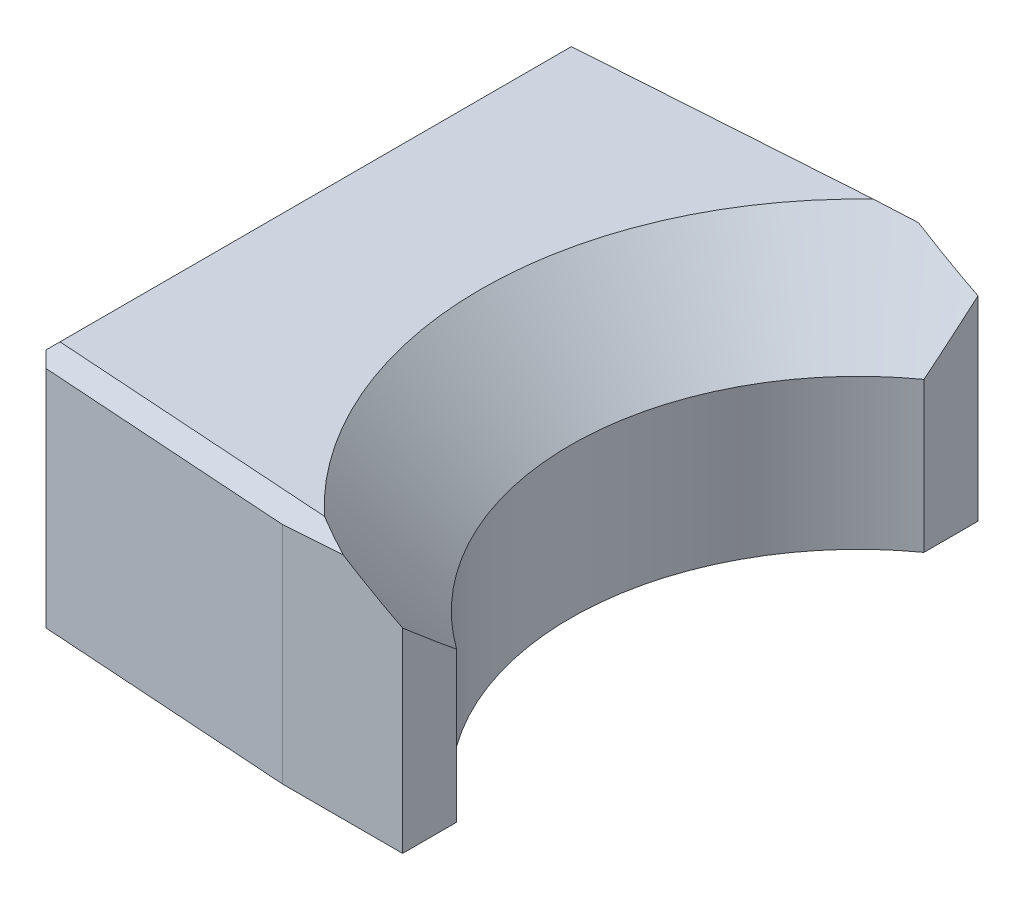
SolidWorks part; units mm, degrees
material "ABS"
ref_plane "Front Plane" through (0, 0, 0) normal (0, 0, 1) x (1, 0, 0)
ref_plane "Top Plane" through (0, 0, 0) normal (0, 1, 0) x (1, 0, 0)
ref_plane "Right Plane" through (0, 0, 0) normal (1, 0, 0) x (0, 0, -1)
sketch "Sketch1" plane through (0, 0, 0) normal (0, 1, 0) x (1, 0, 0)
  line L0 (-28, 48) -> (-48, 48)
  line L2 (-48, -48) -> (-93, -45)
  line L3 (-93, -45) -> (-93, 45)
  line L4 (-93, 45) -> (-48, 48)
  line L6 (-48, -48) -> (-28, -48)
  line L9 (-93, 0) -> (-48, 0) construction
  line L10 (-28, 48) -> (-28, 38.9872)
  line L11 (-28, -38.9872) -> (-28, -48)
  arc A6 (-28, 38.9872) -> (-28, -38.9872) centre (0, 0) ccw
  dimension "D1" = 20
  dimension "D2" = 96
  dimension "D4" = 96
  dimension "D5" = 93
  dimension "D6" = 90
  dimension "D7" = 45
extrude "Boss-Extrude2" add sketch "Sketch1" along normal blind 40
chamfer "Chamfer1" distance 15 angle 45 1 edges at (-48, 40, 0)
chamfer "Chamfer2" distance 2.5 angle 45 3 edges at (-70.5, 40, -46.5) (-70.5, 40, 46.5) (-93, 40, 0)
chamfer "Chamfer3" distance 2.5 angle 45 2 edges at (-93, 18.75, 45) (-93, 18.75, -45)
sketch "Sketch2" plane through (0, 0, 0) normal (0, -1, 0) x (1, 0, 0)
  line L0 (22, 0) -> (-22, 0) construction
  line L1 (-93, -42.3155) -> (-93, 42.5) construction
  line L2 (-28, 48) -> (-28, 38.9872) construction
  line L3 (-48, 48) -> (-28, 48) construction
  line L4 (-89.5, 41.6786) -> (-48, 44.5) construction
  circle A0 centre (-89.5, 41.6786) radius 0.25
  circle A1 centre (-48, 44.5) radius 0.25
  circle A2 centre (-31.5, 44.5) radius 0.25
  circle A3 centre (-89.5, 0) radius 0.25
  circle A4 centre (-69.5, 0) radius 0.25
  circle A5 centre (-54.5, 0) radius 0.25
  circle A6 centre (-68.75, 43.0893) radius 0.25
  circle A7 centre (-48, -44.5) radius 0.25
  circle A8 centre (-31.5, -44.5) radius 0.25
  circle A9 centre (-68.75, -43.0893) radius 0.25
  circle A10 centre (-89.5, -41.6786) radius 0.25
  dimension "D4" = 0.5
  dimension "D5" = 0.5
  dimension "D10" = 0.5
  dimension "D11" = 0.5
  dimension "D13" = 0.5
  dimension "D15" = 0.5
  dimension "D16" = 0.5
  dimension "D1" = 3.5
  dimension "D2" = 3.5
  dimension "D3" = 3.5
  dimension "D6" = 3.5
  dimension "D7" = 0
  dimension "D8" = 3.5
  dimension "D9" = 3.5
  dimension "D12" = 20
  dimension "D14" = 15
hole_wizard "M4x0.7 Tapped Hole1" positions "3DSketch1" profile "Sketch3" tap size "M4x0.7" standard "ANSI Metric"
sketch3d "3DSketch1"
  point P0 (-89.5, 0, 41.6786)
  point P3 (-68.75, 0, 43.0893)
  point P6 (-48, 0, 44.5)
  point P9 (-31.5, 0, 44.5)
  point P12 (-89.5, 0, -41.6786)
  point P15 (-68.75, 0, -43.0893)
  point P18 (-48, 0, -44.5)
  point P21 (-31.5, 0, -44.5)
  point P24 (-89.5, 0, 0)
  point P27 (-69.5, 0, 0)
  point P30 (-54.5, 0, 0)
sketch "Sketch3" plane through (-89.5, 0, 41.6786) normal (1, 0, 0) x (0, 0, -1)
  line L0 (0, 0) -> (0, 11.0914)
  line L1 (0, 11.0914) -> (1.65, 10.1)
  line L2 (1.65, 10.1) -> (1.65, 0)
  line L5 (1.65, 0) -> (0, 0)
  line L10 (0, 11.0914) -> (-1.65, 10.1) construction
  line L11 (0, -6.35) -> (0, 107.95) construction
  dimension "Tap Drill Dia." = 3.3
  dimension "Tap Drill Depth" = 10.1
  dimension "Drill Angle" = 118
cosmetic thread "Hole Thread1" parameters "D1"=8, "D2"=4
cosmetic thread "Hole Thread2" parameters "D1"=8, "D2"=4
cosmetic thread "Hole Thread3" parameters "D1"=8, "D2"=4
cosmetic thread "Hole Thread4" parameters "D1"=8, "D2"=4
cosmetic thread "Hole Thread5" parameters "D1"=8, "D2"=4
cosmetic thread "Hole Thread6" parameters "D1"=8, "D2"=4
cosmetic thread "Hole Thread7" parameters "D1"=8, "D2"=4
cosmetic thread "Hole Thread8" parameters "D1"=8, "D2"=4
cosmetic thread "Hole Thread9" parameters "D1"=8, "D2"=4
cosmetic thread "Hole Thread10" parameters "D1"=8, "D2"=4
cosmetic thread "Hole Thread11" parameters "D1"=8, "D2"=4
sketch "Sketch4" plane through (-93, 0, 0) normal (-1, 0, 0) x (0, 0, 1)
  line L0 (-42.3155, 18.75) -> (42.5, 18.75) construction
  line L1 (-42.3155, 37.5) -> (-42.3155, 0) construction
  line L2 (42.5, 0) -> (42.5, 37.5) construction
  line L3 (0, -22) -> (0, 22) construction
  circle A0 centre (-19.9077, 18.75) radius 11.5
  circle A1 centre (19.9077, 18.75) radius 11.5
  point P6 (0.0923, 18.75)
  dimension "D1" = 23
  dimension "D2" = 20
extrude "Cut-Extrude1" cut sketch "Sketch4" against normal blind 30
sketch "Sketch5" plane through (0, 0, 0) normal (0, -1, 0) x (1, 0, 0)
  line L0 (22, 0) -> (-22, 0) construction
  line L2 (-93, -42.3155) -> (-93, 42.5) construction
  circle A0 centre (-78, -20) radius 0.8602
  circle A1 centre (-78, 20) radius 0.8602
  dimension "D1" = 20
  dimension "D2" = 15
hole_wizard "M6x1.0 Tapped Hole1" positions "3DSketch2" profile "Sketch6" tap size "M6x1.0" standard "ANSI Metric"
sketch3d "3DSketch2"
  point P0 (-78, 0, 20)
  point P3 (-78, 0, -20)
sketch "Sketch6" plane through (-78, 0, 20) normal (1, 0, 0) x (0, 0, -1)
  line L0 (0, 0) -> (0, 16.5022)
  line L1 (0, 16.5022) -> (2.5, 15)
  line L2 (2.5, 15) -> (2.5, 0)
  line L5 (2.5, 0) -> (0, 0)
  line L10 (0, 16.5022) -> (-2.5, 15) construction
  line L11 (0, -6.35) -> (0, 107.95) construction
  dimension "Tap Drill Dia." = 5
  dimension "Tap Drill Depth" = 15
  dimension "Drill Angle" = 118
cosmetic thread "Hole Thread12" parameters "D1"=12, "D2"=6
cosmetic thread "Hole Thread13" parameters "D1"=12, "D2"=6
